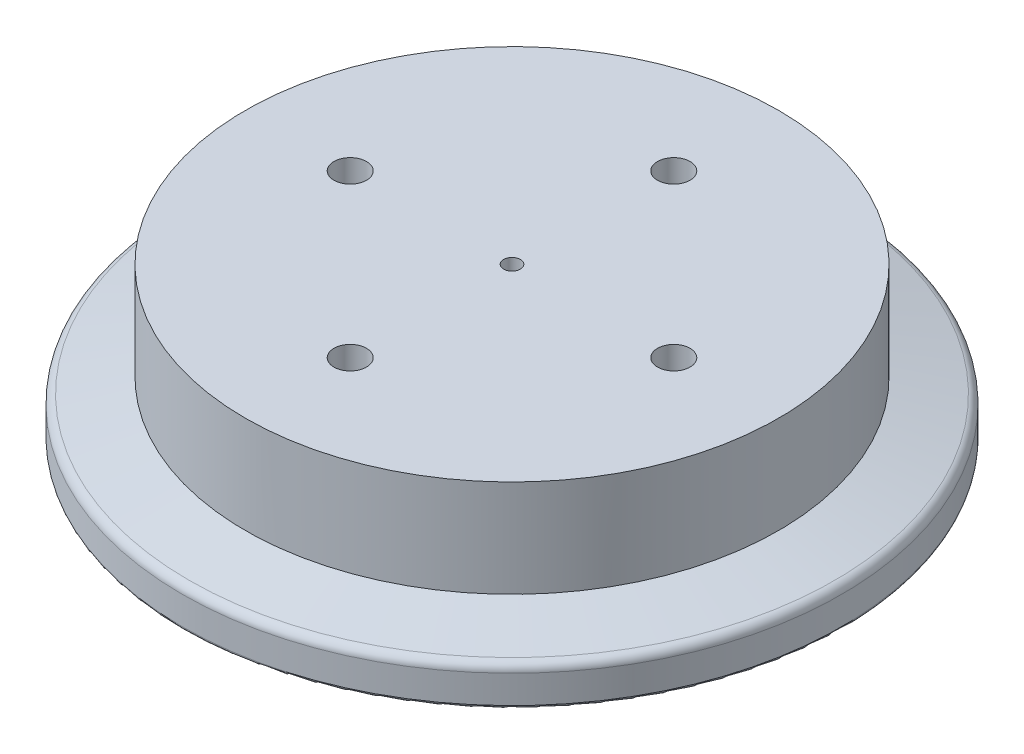
SolidWorks part; units mm, degrees
material "AISI 304"
ref_plane "Front Plane" through (0, 0, 0) normal (0, 0, 1) x (1, 0, 0)
ref_plane "Top Plane" through (0, 0, 0) normal (0, 1, 0) x (1, 0, 0)
ref_plane "Right Plane" through (0, 0, 0) normal (1, 0, 0) x (0, 0, -1)
sketch "Sketch1" plane through (0, 0, 0) normal (1, 0, 0) x (0, 0, -1)
  line L0 (0, 0) -> (0, 5.1) construction
  line L1 (-27.5, 0) -> (-27.5, 3.175)
  line L2 (-27.5, 3.175) -> (-20.3158, 5.1)
  line L6 (0, 2.5) -> (-20.625, 2.5)
  line L7 (-20.625, 2.5) -> (-20.625, 0)
  line L8 (-20.625, 0) -> (-27.5, 0)
  line L9 (-20.3158, 5.1) -> (0, 5.1)
  line L10 (0, 5.1) -> (0, 2.5)
  dimension "D1" = 75
  dimension "D2" = 40.6316
  dimension "Flange ID" = 41.25
  dimension "Flange OD" = 55
  dimension "D5" = 3.175
  dimension "Flange Height" = 5.1
  dimension "D9" = 2.5
revolve "Flange" add sketch "Sketch1" angle 360 about L0
sketch "Sketch2" plane through (0, 0, 0) normal (1, 0, 0) x (0, 0, -1)
  line L0 (0, 2.5) -> (-20.625, 2.5) construction
  line L1 (0, 0) -> (-15.85, 0)
  line L2 (0, 0) -> (0, 2.5)
  line L3 (0, 2.5) -> (-15.85, 2.5)
  line L4 (-15.85, 0) -> (-15.85, 2.5)
  line L5 (0, 0) -> (0, -4.8376) construction
  dimension "ID" = 31.7
revolve "Blank Insert" add sketch "Sketch2" angle 360 about L5
sketch "Sketch5" plane through (0, 2.5, 0) normal (0, -1, 0) x (1, 0, 0)
  circle A0 centre (0, 0) radius 22.25
  dimension "D1" = 44.5
extrude "Stub" add sketch "Sketch5" against normal offset from surface (10.2 mm away) 12.7 up to face at (0, 0, -20.625)
ref_plane "Plane1" through (0, -1.905, 0) normal (0, -1, 0) x (-1, 0, 0)
ref_plane "Plane2" through (0, 2.5, 0) normal (0, -1, 0) x (-1, 0, 0)
ref_plane "Plane3" through (0, 5.1, 0) normal (0, -1, 0) x (-1, 0, 0)
fillet "Fillet1" radius 0.762 1 edges at (0, 3.175, -27.5)
fillet "Fillet2" radius 0.254 1 edges at (0, 0, -27.5)
sketch "Sketch6" plane through (0, 12.7, 0) normal (0, 1, 0) x (1, 0, 0)
  line L0 (0, -22.25) -> (0, 22.25) construction
  line L1 (-22.25, 0) -> (22.25, 0) construction
  circle A0 centre (0, 0) radius 22.25 construction
  circle A1 centre (0, 0) radius 0.6985
extrude "Cut-Extrude1" cut sketch "Sketch6" against normal blind 304.8
sketch "Sketch7" plane through (0, 12.7, 0) normal (0, 1, 0) x (1, 0, 0)
  line L0 (0, -22.25) -> (0, 22.25) construction
  line L1 (-17.6866, 13.4998) -> (17.6866, 13.4998) construction
  circle A0 centre (0, 0) radius 22.25 construction
  circle A1 centre (0, 0) radius 22.25 construction
  circle A2 centre (0, 13.4998) radius 1.3589
  circle A3 centre (13.4998, 0) radius 1.3589
  circle A4 centre (0, -13.4998) radius 1.3589
  circle A5 centre (-13.4998, 0) radius 1.3589
  point P20 (0, 0)
  dimension "D1" = 4
extrude "Cut-Extrude3" cut sketch "Sketch7" against normal blind 4.7625
